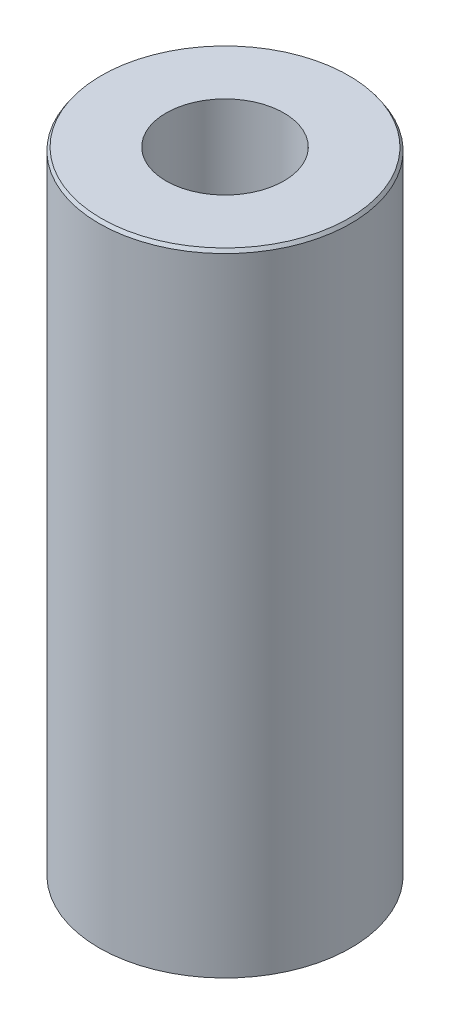
SolidWorks part; units mm, degrees
ref_plane "Front Plane" through (0, 0, 0) normal (0, 0, 1) x (1, 0, 0)
ref_plane "Top Plane" through (0, 0, 0) normal (0, 1, 0) x (1, 0, 0)
ref_plane "Right Plane" through (0, 0, 0) normal (1, 0, 0) x (0, 0, -1)
sketch "Sketch1" plane through (0, 0, 0) normal (0, 1, 0) x (1, 0, 0)
  circle A0 centre (0, 0) radius 47.5
  dimension "SHAFT_OD" = 95
extrude "Boss-Extrude1" add sketch "Sketch1" along normal blind 238.6731
sketch "Sketch2" plane through (0, 0, 0) normal (0, 1, 0) x (1, 0, 0)
  circle A0 centre (0, 0) radius 22.2229
  dimension "BORE_D" = 44.4458
extrude "Cut-Extrude1" cut sketch "Sketch2" along normal through all
chamfer "Chamfer1" distance 1.2429 angle 33.807 2 edges at (0, 238.6731, 47.5) (0, 0, 47.5) first distance on face at (0, 238.6731, 47.5) first distance on face at (0, 0, 22.2229)
